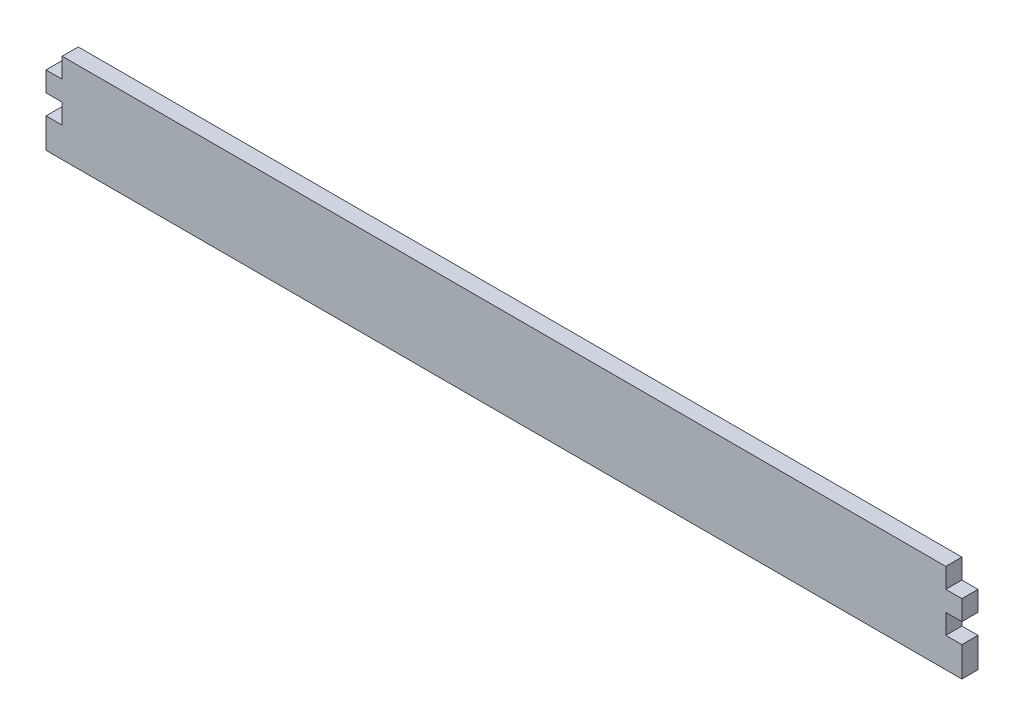
SolidWorks part; units mm, degrees
ref_plane "Ön Düzlem" through (0, 0, 0) normal (0, 0, 1) x (1, 0, 0)
ref_plane "Üst Düzlem" through (0, 0, 0) normal (0, 1, 0) x (1, 0, 0)
ref_plane "Sağ Düzlem" through (0, 0, 0) normal (1, 0, 0) x (0, 0, -1)
sketch "Sketch1" plane through (0, 0, 0) normal (0, 0, 1) x (1, 0, 0)
  line L0 (-76.7, -1.6667) -> (-76.7, 1.6667)
  line L3 (74, 5) -> (-74, 5)
  line L5 (76.7, 1.6667) -> (74, 1.6667)
  line L6 (-74, -1.6667) -> (-74, -5)
  line L8 (76.7, -1.6667) -> (76.7, 1.6667)
  line L10 (-76.7, 1.6667) -> (-74, 1.6667)
  line L11 (-74, 1.6667) -> (-74, 5)
  line L12 (-76.7, -1.6667) -> (-74, -1.6667)
  line L13 (74, 1.6667) -> (74, 5)
  line L14 (76.7, -1.6667) -> (74, -1.6667)
  line L15 (74, -1.6667) -> (74, -5)
  line L16 (-74, -5) -> (-76.7, -5)
  line L17 (-76.7, -5) -> (-76.7, -10)
  line L18 (-76.7, -10) -> (76.7, -10)
  line L19 (76.7, -10) -> (76.7, -5)
  line L20 (76.7, -5) -> (74, -5)
  point P0 (0, 0)
extrude "Boss-Extrude1" add sketch "Sketch1" along normal blind 2.7
